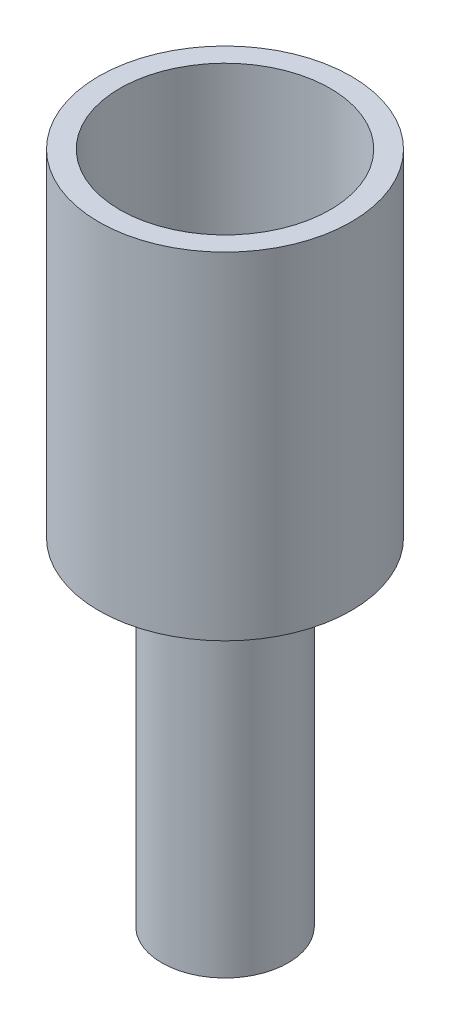
SolidWorks part; units mm, degrees
material "6061-T4 (SS)"
ref_plane "Front Plane" through (0, 0, 0) normal (0, 0, 1) x (1, 0, 0)
ref_plane "Top Plane" through (0, 0, 0) normal (0, 1, 0) x (1, 0, 0)
ref_plane "Right Plane" through (0, 0, 0) normal (1, 0, 0) x (0, 0, -1)
sketch "Sketch1" plane through (0, 0, 0) normal (0, 0, 1) x (1, 0, 0)
  line L0 (-9.525, 25.4) -> (-9.525, 0)
  line L1 (-9.525, 0) -> (-4.7625, 0)
  line L2 (-4.7625, 0) -> (-4.7625, -25.4)
  line L3 (0, -15.8578) -> (0, 15.6451) construction
  point P7 (0, -15.8578)
  point P8 (0, 0)
  point P9 (0, 15.6451)
  point P10 (0, 0)
  point P11 (0, 0)
  point P12 (0, 0)
  dimension "D1" = 9.525
  dimension "D2" = 19.05
  dimension "D3" = 25.4
  dimension "D4" = 25.4
sketch "Sketch2" plane through (0, 0, 0) normal (0, 1, 0) x (1, 0, 0)
  circle A0 centre (0, 0) radius 9.525
  circle A1 centre (0, 0) radius 4.7625
extrude "Boss-Extrude1" add sketch "Sketch2" along normal up to vertex (25.4 mm away) contours A0 A1 | A1 | A1 | A0 region at (-9.2556, 0, 0) region at (0, 0, 0) up to point (-9.525, 25.4, 0)
extrude "Boss-Extrude2" add sketch "Sketch2<3>" against normal up to vertex (25.4 mm away) contours A1 region at (0, 0, 0) up to point (-4.7625, -25.4, 0)
sketch "Sketch2<3>" plane through (0, 0, 0) normal (0, 1, 0) x (1, 0, 0) same geometry as "Sketch2"
sketch "Sketch7" plane through (0, 25.4, 0) normal (0, 1, 0) x (1, 0, 0)
  point P0 (0, 0)
hole_wizard "5/8 (0.625) Diameter Hole1" positions "Sketch7" profile "Sketch6" hole size "5/8" standard "ANSI Inch"
sketch "Sketch6" plane through (0, 25.4, 0) normal (1, 0, 0) x (0, 0, 1)
  line L0 (0, 0) -> (0, 25.4)
  line L1 (0, 25.4) -> (7.9375, 20.6307)
  line L2 (7.9375, 20.6307) -> (7.9375, 0)
  line L5 (7.9375, 0) -> (0, 0)
  line L10 (0, 25.4) -> (-7.9375, 20.6307) construction
  line L11 (0, -6.35) -> (0, 107.95) construction
  dimension "Hole Dia." = 15.875
  dimension "Hole Depth" = 25.4
  dimension "Drill Angle" = 118
sketch "Sketch10" plane through (0, -25.4, 0) normal (0, -1, 0) x (-1, 0, 0)
  point P0 (0, 0)
hole_wizard "1/4 (0.25) Diameter Hole1" positions "Sketch10" profile "Sketch11" hole size "1/4" standard "ANSI Inch" end condition through all
sketch "Sketch11" plane through (0, -25.4, 0) normal (1, 0, 0) x (0, 0, -1)
  line L0 (0, 0) -> (0, 50.8)
  line L1 (0, 50.8) -> (3.175, 50.8)
  line L2 (3.175, 50.8) -> (3.175, 0)
  line L5 (3.175, 0) -> (0, 0)
  line L11 (0, -6.35) -> (0, 107.95) construction
  dimension "Thru Hole Dia." = 6.35
  dimension "Thru Hole Depth" = 50.8
